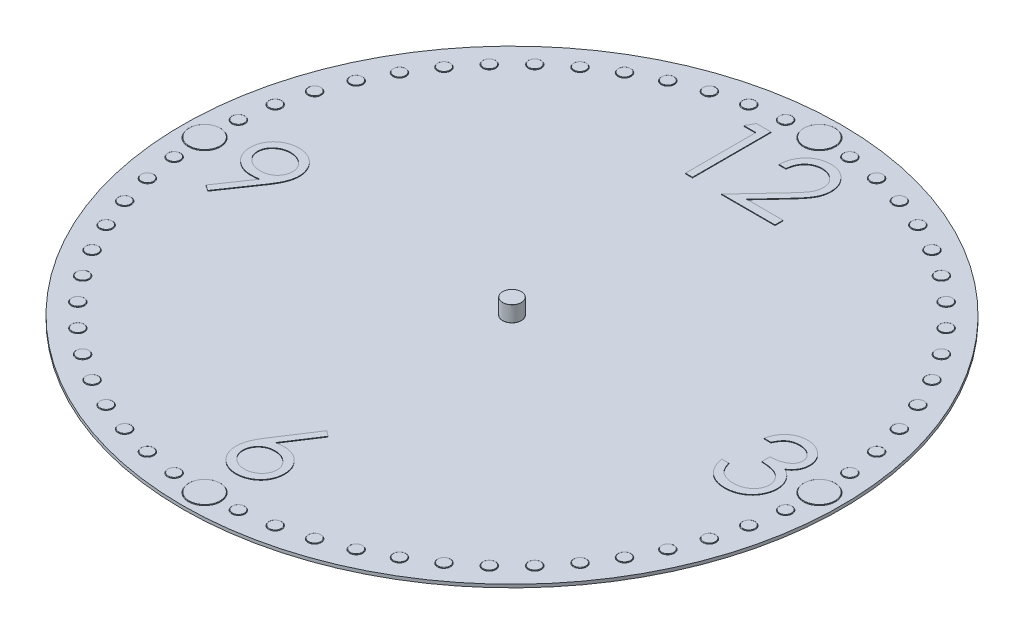
SolidWorks part; units mm, degrees
ref_plane "Front Plane" through (0, 0, 0) normal (0, 0, 1) x (1, 0, 0)
ref_plane "Top Plane" through (0, 0, 0) normal (0, 1, 0) x (1, 0, 0)
ref_plane "Right Plane" through (0, 0, 0) normal (1, 0, 0) x (0, 0, -1)
sketch "Sketch1" plane through (0, 0, 0) normal (0, 1, 0) x (1, 0, 0)
  circle A0 centre (0, 0) radius 13.335
  dimension "D1" = 26.67
extrude "Extrude1" add sketch "Sketch1" along normal blind 0.127
sketch "Sketch2" plane through (0, 0.127, 0) normal (0, 1, 0) x (-1, 0, 0)
  circle A0 centre (0, -12.4392) radius 0.635
  dimension "D1" = 1.27
extrude "Extrude2" add sketch "Sketch2" along normal blind 0.0254
fillet "Fillet1" radius 0.0127 2 edges at (0, 0.127, -11.8042) (0, 0.1524, -11.8042)
sketch "Sketch4" plane through (0, 0, 0) normal (0, 0, 1) x (1, 0, 0)
  line L0 (0, 0) -> (0, 0.4205) construction
pattern_circular "CirPattern1" count 4 over 360 about axis through (0, 0, 0) along (0, 1, 0) of "Extrude2", "Fillet1"
sketch "Sketch5" plane through (0, 0.127, 0) normal (0, 1, 0) x (-1, 0, 0)
  line L0 (0, -12.4392) -> (0, 0) construction
  line L1 (0, 0) -> (-1.9264, -18.3289) construction
  circle A0 centre (0, 0) radius 12.4392 construction
  circle A1 centre (-1.3003, -12.3711) radius 0.254
  dimension "D2" = 0.508
  dimension "D1" = 6
extrude "Extrude3" add sketch "Sketch5" along normal blind 0.0254
fillet "Fillet2" radius 0.0127 2 edges at (1.3003, 0.1524, -12.1171) (1.3003, 0.127, -12.1171)
pattern_circular "CirPattern2" count 60 over 360 about axis through (0, 0, 0) along (0, 1, 0) skipping 1, 16, 31, 46 of "Extrude3", "Fillet2"
sketch "Sketch6" plane through (0, 0.127, 0) normal (0, 1, 0) x (-1, 0, 0)
  circle A0 centre (0, 0) radius 0.381
  dimension "D1" = 0.762
sketch "Sketch9" plane through (0, 0, 0) normal (0, 1, 0) x (1, 0, 0)
  text T1 "12"
extrude "Extrude13" add sketch "Sketch6" along normal blind 0.635
wrap "Wrap2" sketch "Sketch9" wrap type scribe source sketch "Sketch9" face at (1.3003, 0.127, -12.1044)
sketch "Sketch16" plane through (0, 0, 0) normal (0, 1, 0) x (1, 0, 0)
  text T0 "9\r\n"
wrap "Wrap3" sketch "Sketch16" wrap type scribe source sketch "Sketch16" face at (-1.4785, 0.127, -10.4688)
sketch "Sketch25" plane through (0, 0, 0) normal (0, 1, 0) x (1, 0, 0)
  text T0 "6\r\n"
wrap "Wrap4" sketch "Sketch25" wrap type scribe source sketch "Sketch25" face at (1.2082, 0.127, -9.9933)
sketch "Sketch29" plane through (0, 0, 0) normal (0, 1, 0) x (1, 0, 0)
  text T0 "3\r\n"
wrap "Wrap5" sketch "Sketch29" wrap type scribe source sketch "Sketch29"
sketch "Sketch27" plane through (0, 0.127, 0) normal (0, 1, 0) x (1, 0, 0)
  line L3 (0.3261, -7.8196) -> (-0.6216, -9.2685)
  line L4 (0.5455, -7.992) -> (0.3261, -7.8196)
  line L5 (-0.2934, -9.2748) -> (0.5455, -7.992)
  line L6 (0.3261, -7.8196) -> (-0.6216, -9.2685)
  line L7 (0.5455, -7.992) -> (0.3261, -7.8196)
  line L8 (-0.2934, -9.2748) -> (0.5455, -7.992)
  spline S4 degree 3 poles (169.9791, -3005.9549) (-7.8632, 10.3363) (-3.2139, -11.2264) (0.1384, -10.8215) (0.2038, -10.8069) (0.2664, -10.7862) (0.3268, -10.761) (0.384, -10.729) (0.4385, -10.691) (0.49, -10.6482) (0.5377, -10.6016) (0.5788, -10.5515) (0.6139, -10.4992) (0.6424, -10.4446) (0.6651, -10.3873) (0.6807, -10.3277) (1.1283, -7.5783) (-22.7687, -2.839) (2990.9953, -249.0063) knots -9.527484 -9.527484 -9.527484 -9.527484 0.067962 0.133283 0.197835 0.260892 0.323377 0.38635 0.449638 0.514795 0.57924 0.641814 0.701359 0.760727 0.819222 0.878716 0.938147 8.835 8.835 8.835 8.835 only from (0.0005, -10.8318) to (0.6924, -10.2022)
  spline S5 degree 3 poles (-2499.3081, 1650.7062) (17.4996, -4.4596) (3.0537, -3.4263) (-0.7133, -9.4118) (-0.7535, -9.4805) (-0.7905, -9.546) (-0.8226, -9.6094) (-0.8526, -9.669) (-0.8768, -9.727) (-0.9059, -9.7989) (-0.9334, -9.8867) (-0.9579, -9.9901) (-1.5455, -13.8784) (24.3647, -19.7976) (-2992.663, 211.5949) knots -20.907275 -20.907275 -20.907275 -20.907275 0.087622 0.171402 0.250166 0.325701 0.396343 0.462726 0.525528 0.584189 0.694724 0.800274 0.902182 12.434052 12.434052 12.434052 12.434052 only from (-0.6216, -9.2685) to (-0.9765, -10.1907)
  spline S6 degree 3 poles (-258.6624, 2979.4182) (13.1071, -40.3097) (-3.2002, 23.2871) (-7.566, -43.3144) (-289.8247, 2976.5743) knots -46.482215 -46.482215 -46.482215 -46.482215 0.487341 48.273881 48.273881 48.273881 48.273881 only from (0.0354, -9.2443) to (-0.2934, -9.2748)
  spline S7 degree 3 poles (2995.0429, 176.393) (-24.0353, -19.5314) (1.4984, -13.9156) (0.9619, -9.9946) (0.9401, -9.9045) (0.9103, -9.8184) (0.8718, -9.7362) (0.8245, -9.6582) (0.7681, -9.5843) (0.7044, -9.5148) (0.6342, -9.4519) (0.5602, -9.3957) (0.4816, -9.3495) (0.3997, -9.3109) (0.3141, -9.2807) (0.2245, -9.26) (-3.6259, -8.7176) (-9.3454, -34.5352) (204.3295, 2983.6417) knots -7.793325 -7.793325 -7.793325 -7.793325 0.065659 0.129258 0.191437 0.252717 0.31332 0.37449 0.436909 0.500928 0.564976 0.627137 0.688454 0.749057 0.809933 0.871595 0.934769 8.657147 8.657147 8.657147 8.657147 only from (0.9774, -10.185) to (0.0354, -9.2443)
  spline S8 degree 3 poles (275.617, -2998.3814) (-11.4415, 20.002) (-4.0366, -11.959) (0.2468, -11.1276) (0.3714, -11.0868) (0.49, -11.03) (0.6002, -10.9605) (0.6977, -10.8773) (0.7828, -10.7841) (0.8527, -10.6788) (0.9089, -10.5655) (0.9482, -10.4442) (1.7782, -6.2687) (-31.0303, 1.1492) (2987.7444, -289.4489) knots -8.162033 -8.162033 -8.162033 -8.162033 0.085972 0.169956 0.254217 0.339243 0.423978 0.505828 0.586636 0.66771 0.749601 0.830875 0.914052 8.960034 8.960034 8.960034 8.960034 only from (-0.0148, -11.1574) to (0.9774, -10.185)
  spline S9 degree 3 poles (-2989.2364, -273.907) (29.3041, 0.935) (-1.7585, -6.2065) (-0.9475, -10.4433) (-0.9065, -10.5639) (-0.8518, -10.6796) (-0.7829, -10.7872) (-0.7001, -10.8825) (-0.6057, -10.9656) (-0.5002, -11.0346) (-0.3863, -11.0892) (-0.2666, -11.1289) (3.8585, -11.9394) (11.0596, 19.9916) (-272.2933, -2998.7105) knots -8.234795 -8.234795 -8.234795 -8.234795 0.084361 0.16749 0.250533 0.3354 0.419627 0.502172 0.584085 0.66726 0.750434 0.832948 0.915665 9.020067 9.020067 9.020067 9.020067 only from (-0.9765, -10.1907) to (-0.0148, -11.1574)
  spline S10 degree 3 poles (-0.6216, -9.2685) (-0.6375, -9.293) (-0.6688, -9.3411) (-0.7133, -9.4118) (-0.7535, -9.4805) (-0.7905, -9.546) (-0.8226, -9.6094) (-0.8526, -9.669) (-0.8768, -9.727) (-0.9059, -9.7989) (-0.9334, -9.8867) (-0.9579, -9.9901) (-0.9732, -10.0912) (-0.9754, -10.158) (-0.9765, -10.1907) knots 0 0 0 0 0.087622 0.171402 0.250166 0.325701 0.396343 0.462726 0.525528 0.584189 0.694724 0.800274 0.902182 1 1 1 1
  spline S11 degree 3 poles (0.0354, -9.2443) (-0.0183, -9.2457) (-0.1286, -9.2486) (-0.2375, -9.2659) (-0.2934, -9.2748) knots 0 0 0 0 0.487341 1 1 1 1
  spline S12 degree 3 poles (0.9774, -10.185) (0.9765, -10.1525) (0.9747, -10.0886) (0.9619, -9.9946) (0.9401, -9.9045) (0.9103, -9.8184) (0.8718, -9.7362) (0.8245, -9.6582) (0.7681, -9.5843) (0.7044, -9.5148) (0.6342, -9.4519) (0.5602, -9.3957) (0.4816, -9.3495) (0.3997, -9.3109) (0.3141, -9.2807) (0.2245, -9.26) (0.1312, -9.2469) (0.0677, -9.2452) (0.0354, -9.2443) knots 0 0 0 0 0.065659 0.129258 0.191437 0.252717 0.31332 0.37449 0.436909 0.500928 0.564976 0.627137 0.688454 0.749057 0.809933 0.871595 0.934769 1 1 1 1
  spline S13 degree 3 poles (-0.0148, -11.1574) (0.0296, -11.1559) (0.1174, -11.1527) (0.2468, -11.1276) (0.3714, -11.0868) (0.49, -11.03) (0.6002, -10.9605) (0.6977, -10.8773) (0.7828, -10.7841) (0.8527, -10.6788) (0.9089, -10.5655) (0.9482, -10.4442) (0.9736, -10.3168) (0.9761, -10.2294) (0.9774, -10.185) knots 0 0 0 0 0.085972 0.169956 0.254217 0.339243 0.423978 0.505828 0.586636 0.66771 0.749601 0.830875 0.914052 1 1 1 1
  spline S14 degree 3 poles (-0.9765, -10.1907) (-0.9748, -10.2334) (-0.9714, -10.3182) (-0.9475, -10.4433) (-0.9065, -10.5639) (-0.8518, -10.6796) (-0.7829, -10.7872) (-0.7001, -10.8825) (-0.6057, -10.9656) (-0.5002, -11.0346) (-0.3863, -11.0892) (-0.2666, -11.1289) (-0.1422, -11.1533) (-0.0575, -11.1561) (-0.0148, -11.1574) knots 0 0 0 0 0.084361 0.16749 0.250533 0.3354 0.419627 0.502172 0.584085 0.66726 0.750434 0.832948 0.915665 1 1 1 1
  spline S15 degree 3 poles (2988.8667, 254.5542) (-23.8611, -17.6816) (1.1513, -12.7264) (0.6799, -10.0756) (0.6645, -10.0155) (0.6413, -9.9578) (0.6112, -9.9029) (0.5744, -9.8505) (0.532, -9.8001) (0.4829, -9.7534) (0.4295, -9.7106) (0.3727, -9.6728) (0.3132, -9.641) (0.2512, -9.6144) (0.186, -9.5952) (0.1185, -9.5801) (-3.3998, -9.1793) (-7.9862, -30.4824) (140.2087, 2986.9965) knots -7.403749 -7.403749 -7.403749 -7.403749 0.061138 0.119994 0.178225 0.236256 0.294929 0.354716 0.41673 0.480664 0.545832 0.609758 0.672971 0.736017 0.799839 0.864775 0.931088 10.779567 10.779567 10.779567 10.779567 only from (0.6924, -10.2022) to (-0.0243, -9.5699)
  spline S16 degree 3 poles (-140.2945, 2987.0276) (7.8507, -30.5806) (3.3064, -9.1791) (-0.1651, -9.58) (-0.2307, -9.5951) (-0.2934, -9.6143) (-0.3522, -9.6407) (-0.4073, -9.6728) (-0.4591, -9.7105) (-0.5069, -9.7535) (-0.5503, -9.8004) (-0.5877, -9.8507) (-0.6199, -9.9032) (-0.6461, -9.9582) (-0.6665, -10.0158) (-0.6813, -10.0756) (-1.0857, -13.1538) (20.4729, -17.6016) (-2995.1872, 170.2015) knots -9.973756 -9.973756 -9.973756 -9.973756 0.070599 0.137901 0.203196 0.26679 0.329106 0.390654 0.452653 0.515748 0.577926 0.63893 0.698351 0.757296 0.816394 0.876267 0.936817 9.857126 9.857126 9.857126 9.857126 only from (-0.0243, -9.5699) to (-0.6915, -10.2022)
  spline S17 degree 3 poles (-2990.7427, -253.2228) (22.7923, -2.8091) (-1.1279, -7.5816) (-0.6797, -10.3277) (-0.6643, -10.3873) (-0.6413, -10.4443) (-0.6139, -10.4996) (-0.5777, -10.551) (-0.5376, -10.6019) (-0.4896, -10.6481) (-0.4382, -10.6912) (-0.3832, -10.7288) (-0.3259, -10.761) (-0.2655, -10.7862) (-0.2029, -10.8069) (-0.1375, -10.8215) (3.2146, -11.2264) (7.8659, 10.3372) (-170.2687, -3005.9248) knots -7.825614 -7.825614 -7.825614 -7.825614 0.061842 0.121262 0.180746 0.239231 0.298308 0.358183 0.420359 0.484792 0.549938 0.613718 0.676681 0.739154 0.8022 0.86674 0.93205 10.525288 10.525288 10.525288 10.525288 only from (-0.6915, -10.2022) to (0.0005, -10.8318)
  spline S18 degree 3 poles (0.0005, -10.8318) (0.024, -10.8311) (0.0702, -10.8297) (0.1384, -10.8215) (0.2038, -10.8069) (0.2664, -10.7862) (0.3268, -10.761) (0.384, -10.729) (0.4385, -10.691) (0.49, -10.6482) (0.5377, -10.6016) (0.5788, -10.5515) (0.6139, -10.4992) (0.6424, -10.4446) (0.6651, -10.3873) (0.6807, -10.3277) (0.6908, -10.2657) (0.6919, -10.2236) (0.6924, -10.2022) knots 0 0 0 0 0.067962 0.133283 0.197835 0.260892 0.323377 0.38635 0.449638 0.514795 0.57924 0.641814 0.701359 0.760727 0.819222 0.878716 0.938147 1 1 1 1
  spline S19 degree 3 poles (0.6924, -10.2022) (0.6919, -10.1805) (0.691, -10.1379) (0.6799, -10.0756) (0.6645, -10.0155) (0.6413, -9.9578) (0.6112, -9.9029) (0.5744, -9.8505) (0.532, -9.8001) (0.4829, -9.7534) (0.4295, -9.7106) (0.3727, -9.6728) (0.3132, -9.641) (0.2512, -9.6144) (0.186, -9.5952) (0.1185, -9.5801) (0.0479, -9.5721) (0.0001, -9.5707) (-0.0243, -9.5699) knots 0 0 0 0 0.061138 0.119994 0.178225 0.236256 0.294929 0.354716 0.41673 0.480664 0.545832 0.609758 0.672971 0.736017 0.799839 0.864775 0.931088 1 1 1 1
  spline S20 degree 3 poles (-0.0243, -9.5699) (-0.0485, -9.5707) (-0.0958, -9.572) (-0.1651, -9.58) (-0.2307, -9.5951) (-0.2934, -9.6143) (-0.3522, -9.6407) (-0.4073, -9.6728) (-0.4591, -9.7105) (-0.5069, -9.7535) (-0.5503, -9.8004) (-0.5877, -9.8507) (-0.6199, -9.9032) (-0.6461, -9.9582) (-0.6665, -10.0158) (-0.6813, -10.0756) (-0.6895, -10.1381) (-0.6908, -10.1805) (-0.6915, -10.2022) knots 0 0 0 0 0.070599 0.137901 0.203196 0.26679 0.329106 0.390654 0.452653 0.515748 0.577926 0.63893 0.698351 0.757296 0.816394 0.876267 0.936817 1 1 1 1
  spline S21 degree 3 poles (-0.6915, -10.2022) (-0.691, -10.2236) (-0.6898, -10.2657) (-0.6797, -10.3277) (-0.6643, -10.3873) (-0.6413, -10.4443) (-0.6139, -10.4996) (-0.5777, -10.551) (-0.5376, -10.6019) (-0.4896, -10.6481) (-0.4382, -10.6912) (-0.3832, -10.7288) (-0.3259, -10.761) (-0.2655, -10.7862) (-0.2029, -10.8069) (-0.1375, -10.8215) (-0.0693, -10.8297) (-0.0231, -10.8311) (0.0005, -10.8318) knots 0 0 0 0 0.061842 0.121262 0.180746 0.239231 0.298308 0.358183 0.420359 0.484792 0.549938 0.613718 0.676681 0.739154 0.8022 0.86674 0.93205 1 1 1 1
  dimension "D1" = 0
  dimension "D2" = 0
extrude "Extrude18" add sketch "Sketch27" along normal blind 0.0254
sketch "Sketch20" plane through (0, 0.127, 0) normal (0, 1, 0) x (1, 0, 0)
  line L3 (-10.5003, -1.8117) -> (-9.5227, -0.3819)
  line L4 (-10.728, -1.6533) -> (-10.5003, -1.8117)
  line L5 (-9.8452, -0.3628) -> (-10.728, -1.6533)
  line L6 (-10.5003, -1.8117) -> (-9.5227, -0.3819)
  line L7 (-10.728, -1.6533) -> (-10.5003, -1.8117)
  line L8 (-9.8452, -0.3628) -> (-10.728, -1.6533)
  spline S4 degree 3 poles (-164.5335, 2997.1407) (-2.1865, -19.8295) (-6.8301, 1.593) (-10.2971, 1.1903) (-10.3641, 1.1754) (-10.4286, 1.1551) (-10.4906, 1.1289) (-10.5499, 1.0971) (-10.6062, 1.0592) (-10.659, 1.0162) (-10.708, 0.9699) (-10.7499, 0.9193) (-10.7858, 0.867) (-10.8156, 0.8124) (-10.8383, 0.755) (-10.8552, 0.6954) (-11.2921, -2.1329) (11.9721, -6.6168) (-3003.8264, 203.8311) knots -9.696381 -9.696381 -9.696381 -9.696381 0.068712 0.134812 0.199538 0.263335 0.326747 0.390328 0.454126 0.519203 0.58351 0.645497 0.70529 0.763488 0.821856 0.880004 0.939108 8.924521 8.924521 8.924521 8.924521 only from (-10.1555, 1.2005) to (-10.8666, 0.5696)
  spline S5 degree 3 poles (2487.2579, -1663.317) (-28.7469, -1.8575) (-12.65, -5.2962) (-9.4279, -0.2372) (-9.3861, -0.1682) (-9.3492, -0.1017) (-9.3148, -0.0385) (-9.2853, 0.0224) (-9.2587, 0.0802) (-9.2305, 0.1534) (-9.2012, 0.2421) (-9.1754, 0.3468) (-8.5901, 4.307) (-34.5404, 10.2167) (2983.1763, -211.6672) knots -17.442044 -17.442044 -17.442044 -17.442044 0.087946 0.171747 0.250583 0.32591 0.396143 0.462994 0.525418 0.583838 0.694397 0.800583 0.90168 12.476684 12.476684 12.476684 12.476684 only from (-9.5227, -0.3819) to (-9.157, 0.5505)
  spline S6 degree 3 poles (187.7732, -2993.6429) (-23.6022, 28.2124) (-7.8166, -30.1038) (-0.5757, 30.4935) (222.3825, -2991.1898) knots -51.049841 -51.049841 -51.049841 -51.049841 0.492142 52.587835 52.587835 52.587835 52.587835 only from (-10.1791, -0.387) to (-9.8452, -0.3628)
  spline S7 degree 3 poles (-3004.3671, -199.4635) (14.6766, 9.8307) (-11.6899, 4.1624) (-11.1354, 0.3632) (-11.1131, 0.2734) (-11.0825, 0.187) (-11.0421, 0.1052) (-10.9936, 0.0266) (-10.9351, -0.047) (-10.8695, -0.1166) (-10.7974, -0.1799) (-10.7205, -0.2352) (-10.6396, -0.2823) (-10.5549, -0.3202) (-10.4664, -0.3507) (-10.374, -0.3712) (-6.4249, -0.9165) (-0.5961, 25.0954) (-213.894, -2993.3167) knots -7.432221 -7.432221 -7.432221 -7.432221 0.064609 0.12725 0.188534 0.248578 0.309139 0.369772 0.431966 0.495825 0.559795 0.622662 0.68409 0.74564 0.807138 0.869869 0.933705 8.725564 8.725564 8.725564 8.725564 only from (-11.1515, 0.5537) to (-10.1791, -0.387)
  spline S8 degree 3 poles (-267.5318, 2990.4136) (1.2514, -29.22) (-6.019, 2.32) (-10.4063, 1.4966) (-10.533, 1.4546) (-10.6539, 1.3977) (-10.7659, 1.3269) (-10.8661, 1.2446) (-10.9524, 1.1506) (-11.0242, 1.0463) (-11.0812, 0.9331) (-11.122, 0.8127) (-11.9531, -3.4468) (20.1884, -10.7958) (-2998.7985, 271.7019) knots -8.280467 -8.280467 -8.280467 -8.280467 0.086062 0.17094 0.255778 0.341735 0.427007 0.509416 0.590092 0.671171 0.751825 0.832673 0.914751 9.049697 9.049697 9.049697 9.049697 only from (-10.1409, 1.5261) to (-11.1515, 0.5537)
  spline S9 degree 3 poles (2977.135, 285.5898) (-40.2348, -10.7025) (-8.356, -3.3421) (-9.1869, 0.8041) (-9.2278, 0.9254) (-9.2845, 1.0417) (-9.3551, 1.1499) (-9.4389, 1.247) (-9.5358, 1.3306) (-9.6435, 1.4007) (-9.7598, 1.4567) (-9.8822, 1.4972) (-14.2129, 2.3112) (-21.453, -29.0003) (251.6617, 2989.9347) knots -7.942459 -7.942459 -7.942459 -7.942459 0.083474 0.165402 0.248081 0.332 0.416297 0.498735 0.580591 0.664318 0.748057 0.830997 0.914468 9.28503 9.28503 9.28503 9.28503 only from (-9.157, 0.5505) to (-10.1409, 1.5261)
  spline S10 degree 3 poles (-9.5227, -0.3819) (-9.5061, -0.3572) (-9.4736, -0.3089) (-9.4279, -0.2372) (-9.3861, -0.1682) (-9.3492, -0.1017) (-9.3148, -0.0385) (-9.2853, 0.0224) (-9.2587, 0.0802) (-9.2305, 0.1534) (-9.2012, 0.2421) (-9.1754, 0.3468) (-9.1602, 0.4495) (-9.1581, 0.5171) (-9.157, 0.5505) knots 0 0 0 0 0.087946 0.171747 0.250583 0.32591 0.396143 0.462994 0.525418 0.583838 0.694397 0.800583 0.90168 1 1 1 1
  spline S11 degree 3 poles (-10.1791, -0.387) (-10.1241, -0.3858) (-10.0124, -0.3833) (-9.9015, -0.3697) (-9.8452, -0.3628) knots 0 0 0 0 0.492142 1 1 1 1
  spline S12 degree 3 poles (-11.1515, 0.5537) (-11.1507, 0.5212) (-11.1491, 0.4572) (-11.1354, 0.3632) (-11.1131, 0.2734) (-11.0825, 0.187) (-11.0421, 0.1052) (-10.9936, 0.0266) (-10.9351, -0.047) (-10.8695, -0.1166) (-10.7974, -0.1799) (-10.7205, -0.2352) (-10.6396, -0.2823) (-10.5549, -0.3202) (-10.4664, -0.3507) (-10.374, -0.3712) (-10.2778, -0.3845) (-10.2124, -0.3862) (-10.1791, -0.387) knots 0 0 0 0 0.064609 0.12725 0.188534 0.248578 0.309139 0.369772 0.431966 0.495825 0.559795 0.622662 0.68409 0.74564 0.807138 0.869869 0.933705 1 1 1 1
  spline S13 degree 3 poles (-10.1409, 1.5261) (-10.1858, 1.5245) (-10.2748, 1.5212) (-10.4063, 1.4966) (-10.533, 1.4546) (-10.6539, 1.3977) (-10.7659, 1.3269) (-10.8661, 1.2446) (-10.9524, 1.1506) (-11.0242, 1.0463) (-11.0812, 0.9331) (-11.122, 0.8127) (-11.1469, 0.6853) (-11.15, 0.5981) (-11.1515, 0.5537) knots 0 0 0 0 0.086062 0.17094 0.255778 0.341735 0.427007 0.509416 0.590092 0.671171 0.751825 0.832673 0.914751 1 1 1 1
  spline S14 degree 3 poles (-9.157, 0.5505) (-9.1586, 0.5934) (-9.1618, 0.6785) (-9.1869, 0.8041) (-9.2278, 0.9254) (-9.2845, 1.0417) (-9.3551, 1.1499) (-9.4389, 1.247) (-9.5358, 1.3306) (-9.6435, 1.4007) (-9.7598, 1.4567) (-9.8822, 1.4972) (-10.01, 1.5212) (-10.0969, 1.5245) (-10.1409, 1.5261) knots 0 0 0 0 0.083474 0.165402 0.248081 0.332 0.416297 0.498735 0.580591 0.664318 0.748057 0.830997 0.914468 1 1 1 1
  spline S15 degree 3 poles (-3002.3399, -224.0732) (12.9244, 7.773) (-11.3112, 3.1582) (-10.8545, 0.4436) (-10.837, 0.384) (-10.8136, 0.3264) (-10.7828, 0.2714) (-10.7449, 0.2192) (-10.7006, 0.1692) (-10.6503, 0.1222) (-10.5952, 0.0791) (-10.5365, 0.0414) (-10.4749, 0.0096) (-10.4105, -0.016) (-10.3435, -0.0365) (-10.2735, -0.0511) (-6.6646, -0.4535) (-1.9005, 20.8521) (-162.1587, -2996.0663) knots -7.443137 -7.443137 -7.443137 -7.443137 0.05954 0.117423 0.17444 0.231734 0.289722 0.3492 0.410516 0.47508 0.540094 0.604444 0.668697 0.73211 0.796739 0.862906 0.930462 10.866089 10.866089 10.866089 10.866089 only from (-10.8666, 0.5696) to (-10.1263, -0.0614)
  spline S16 degree 3 poles (147.0279, -2995.8644) (-18.3349, 21.2679) (-13.5496, -0.4563) (-9.9799, -0.0512) (-9.9119, -0.0367) (-9.8478, -0.0159) (-9.7869, 0.0092) (-9.7302, 0.0411) (-9.6776, 0.0793) (-9.6288, 0.1221) (-9.5855, 0.1697) (-9.5469, 0.2195) (-9.5141, 0.2717) (-9.4882, 0.327) (-9.4669, 0.3841) (-9.4522, 0.4438) (-9.0491, 3.5149) (-30.4358, 7.9819) (2984.6742, -184.942) knots -10.121139 -10.121139 -10.121139 -10.121139 0.072713 0.141547 0.208363 0.272462 0.33539 0.397711 0.459383 0.522098 0.584315 0.644392 0.703345 0.761509 0.82003 0.878517 0.938265 9.721188 9.721188 9.721188 9.721188 only from (-10.1263, -0.0614) to (-9.4419, 0.5696)
  spline S17 degree 3 poles (2983.532, 203.5527) (-32.2797, -6.6148) (-9.0165, -2.1331) (-9.4533, 0.6954) (-9.4702, 0.755) (-9.4929, 0.8124) (-9.5228, 0.867) (-9.5586, 0.9195) (-9.6012, 0.9697) (-9.6502, 1.0162) (-9.703, 1.0592) (-9.7593, 1.0971) (-9.8186, 1.1289) (-9.8805, 1.1551) (-9.9453, 1.1755) (-10.0127, 1.1903) (-13.5065, 1.5934) (-18.1865, -19.8522) (145.3202, 2997.0521) knots -7.907648 -7.907648 -7.907648 -7.907648 0.06076 0.119735 0.177757 0.235999 0.29407 0.353733 0.415973 0.48014 0.545076 0.608735 0.672178 0.735453 0.799112 0.864284 0.930837 10.749561 10.749561 10.749561 10.749561 only from (-9.4419, 0.5696) to (-10.1555, 1.2005)
  spline S18 degree 3 poles (-10.1555, 1.2005) (-10.1797, 1.1998) (-10.2272, 1.1984) (-10.2971, 1.1903) (-10.3641, 1.1754) (-10.4286, 1.1551) (-10.4906, 1.1289) (-10.5499, 1.0971) (-10.6062, 1.0592) (-10.659, 1.0162) (-10.708, 0.9699) (-10.7499, 0.9193) (-10.7858, 0.867) (-10.8156, 0.8124) (-10.8383, 0.755) (-10.8552, 0.6954) (-10.8648, 0.6333) (-10.866, 0.591) (-10.8666, 0.5696) knots 0 0 0 0 0.068712 0.134812 0.199538 0.263335 0.326747 0.390328 0.454126 0.519203 0.58351 0.645497 0.70529 0.763488 0.821856 0.880004 0.939108 1 1 1 1
  spline S19 degree 3 poles (-10.8666, 0.5696) (-10.8661, 0.5481) (-10.865, 0.5058) (-10.8545, 0.4436) (-10.837, 0.384) (-10.8136, 0.3264) (-10.7828, 0.2714) (-10.7449, 0.2192) (-10.7006, 0.1692) (-10.6503, 0.1222) (-10.5952, 0.0791) (-10.5365, 0.0414) (-10.4749, 0.0096) (-10.4105, -0.016) (-10.3435, -0.0365) (-10.2735, -0.0511) (-10.2007, -0.0593) (-10.1513, -0.0607) (-10.1263, -0.0614) knots 0 0 0 0 0.05954 0.117423 0.17444 0.231734 0.289722 0.3492 0.410516 0.47508 0.540094 0.604444 0.668697 0.73211 0.796739 0.862906 0.930462 1 1 1 1
  spline S20 degree 3 poles (-10.1263, -0.0614) (-10.101, -0.0607) (-10.0519, -0.0593) (-9.9799, -0.0512) (-9.9119, -0.0367) (-9.8478, -0.0159) (-9.7869, 0.0092) (-9.7302, 0.0411) (-9.6776, 0.0793) (-9.6288, 0.1221) (-9.5855, 0.1697) (-9.5469, 0.2195) (-9.5141, 0.2717) (-9.4882, 0.327) (-9.4669, 0.3841) (-9.4522, 0.4438) (-9.444, 0.5059) (-9.4426, 0.5481) (-9.4419, 0.5696) knots 0 0 0 0 0.072713 0.141547 0.208363 0.272462 0.33539 0.397711 0.459383 0.522098 0.584315 0.644392 0.703345 0.761509 0.82003 0.878517 0.938265 1 1 1 1
  spline S21 degree 3 poles (-9.4419, 0.5696) (-9.4425, 0.591) (-9.4437, 0.6333) (-9.4533, 0.6954) (-9.4702, 0.755) (-9.4929, 0.8124) (-9.5228, 0.867) (-9.5586, 0.9195) (-9.6012, 0.9697) (-9.6502, 1.0162) (-9.703, 1.0592) (-9.7593, 1.0971) (-9.8186, 1.1289) (-9.8805, 1.1551) (-9.9453, 1.1755) (-10.0127, 1.1903) (-10.0833, 1.1984) (-10.1311, 1.1998) (-10.1555, 1.2005) knots 0 0 0 0 0.06076 0.119735 0.177757 0.235999 0.29407 0.353733 0.415973 0.48014 0.545076 0.608735 0.672178 0.735453 0.799112 0.864284 0.930837 1 1 1 1
  dimension "D1" = 0
  dimension "D2" = 0
extrude "Extrude16" add sketch "Sketch20" along normal blind 0.0254
sketch "Sketch24" plane through (0, 0.127, 0) normal (0, 1, 0) x (1, 0, 0)
  line L0 (-1.1568, 11.6356) -> (-1.1568, 8.4606) construction
  line L1 (-1.1568, 8.4606) -> (-1.4417, 8.4606) construction
  line L2 (-1.1568, 11.6356) -> (-1.1568, 8.4606)
  line L3 (-1.1568, 8.4606) -> (-1.4417, 8.4606)
  line L4 (-1.4417, 8.4606) -> (-1.4417, 11.31) construction
  line L5 (-1.4417, 11.31) -> (-1.9302, 11.31) construction
  line L6 (-1.9302, 11.31) -> (-1.7438, 11.6356) construction
  line L7 (-1.7438, 11.6356) -> (-1.1568, 11.6356) construction
  line L8 (-1.4417, 8.4606) -> (-1.4417, 11.31)
  line L9 (-1.4417, 11.31) -> (-1.9302, 11.31)
  line L10 (-1.9302, 11.31) -> (-1.7438, 11.6356)
  line L11 (-1.7438, 11.6356) -> (-1.1568, 11.6356)
  line L12 (2.1811, 8.4606) -> (0.0237, 8.4606) construction
  line L13 (2.1811, 8.7863) -> (2.1811, 8.4606) construction
  line L14 (0.7036, 8.7863) -> (2.1811, 8.7863) construction
  line L15 (1.498, 9.6341) -> (0.7036, 8.7863) construction
  line L16 (0.4307, 10.6587) -> (0.1458, 10.6587) construction
  line L17 (0.0237, 8.4606) -> (1.255, 9.7747) construction
  line L18 (2.1811, 8.4606) -> (0.0237, 8.4606)
  line L19 (2.1811, 8.7863) -> (2.1811, 8.4606)
  line L20 (0.7036, 8.7863) -> (2.1811, 8.7863)
  line L21 (1.498, 9.6341) -> (0.7036, 8.7863)
  line L22 (0.4307, 10.6587) -> (0.1458, 10.6587)
  line L23 (0.0237, 8.4606) -> (1.255, 9.7747)
  spline S0 degree 3 poles (1992.8888, -180.7363) (-21.9954, 20.4269) (2.8534, 14.1906) (2.1097, 10.5125) (2.069, 10.3877) (2.0201, 10.2872) (1.9706, 10.2063) (1.9261, 10.1396) (1.874, 10.0679) (1.8135, 9.9912) (1.7459, 9.9091) (1.6706, 9.8216) (-3.9681, 3.6108) (-17.6358, 4.9304) (1447.9539, -1371.4309) knots -8.056366 -8.056366 -8.056366 -8.056366 0.098702 0.195672 0.292422 0.391343 0.444462 0.504229 0.570352 0.642546 0.722288 0.807921 0.90047 19.46034 19.46034 19.46034 19.46034 only from (2.1404, 10.7732) to (1.498, 9.6341) construction
  spline S1 degree 3 poles (126.2886, 2007.7465) (-7.0917, -8.1164) (-2.1637, 12.1896) (1.3843, 11.7009) (1.4793, 11.6793) (1.5694, 11.6491) (1.6538, 11.6085) (1.7331, 11.5597) (1.8083, 11.5033) (1.876, 11.4368) (1.9381, 11.3659) (1.9917, 11.2901) (2.0376, 11.2119) (2.0759, 11.1306) (2.1041, 11.0454) (2.1255, 10.9577) (2.5806, 7.5216) (-16.287, 2.9111) (1998.7713, 125.1206) knots -6.934537 -6.934537 -6.934537 -6.934537 0.069475 0.136517 0.200789 0.26383 0.325735 0.387291 0.449509 0.512968 0.576275 0.63758 0.697903 0.757172 0.816599 0.876653 0.93729 7.720344 7.720344 7.720344 7.720344 only from (1.1812, 11.7171) to (2.1404, 10.7732) construction
  spline S2 degree 3 poles (-1992.0742, 186.1515) (19.9257, 1.3335) (-0.4325, 7.071) (0.1684, 10.879) (0.1928, 10.9825) (0.2274, 11.0803) (0.2703, 11.1734) (0.3218, 11.2614) (0.3827, 11.344) (0.4518, 11.4203) (0.5269, 11.4903) (0.6079, 11.5508) (0.6931, 11.6019) (0.7821, 11.6446) (0.8759, 11.6766) (0.9738, 11.7004) (4.5324, 12.1982) (9.4344, -8.4475) (-118.3449, 2008.0165) knots -6.801028 -6.801028 -6.801028 -6.801028 0.068791 0.135103 0.198979 0.261904 0.323495 0.385195 0.446969 0.509765 0.572251 0.633405 0.693251 0.752583 0.812579 0.873275 0.93555 7.331821 7.331821 7.331821 7.331821 only from (0.1458, 10.6587) to (1.1812, 11.7171) construction
  spline S3 degree 3 poles (-109.3262, 2008.2602) (7.987, -5.4652) (3.9908, 11.7502) (1.0214, 11.3806) (0.9531, 11.3652) (0.888, 11.3442) (0.8258, 11.3175) (0.767, 11.2842) (0.7116, 11.2445) (0.6595, 11.1994) (0.6116, 11.1493) (0.5694, 11.0934) (0.5326, 11.0328) (0.5005, 10.9676) (0.4744, 10.8972) (0.4545, 10.822) (-0.174, 7.6401) (17.6391, 1.9366) (-1982.0079, 274.9879) knots -7.564621 -7.564621 -7.564621 -7.564621 0.064439 0.126547 0.186887 0.245878 0.304041 0.362191 0.420976 0.48066 0.5406 0.600689 0.661936 0.724443 0.789038 0.856314 0.926352 9.195555 9.195555 9.195555 9.195555 only from (1.1666, 11.3914) to (0.4307, 10.6587) construction
  spline S4 degree 3 poles (1995.8262, 165.3949) (-15.9465, 4.4957) (2.2356, 8.4289) (1.8437, 10.8747) (1.8285, 10.9351) (1.8068, 10.9935) (1.7781, 11.0492) (1.7432, 11.1024) (1.7029, 11.1538) (1.6564, 11.202) (1.6052, 11.2462) (1.5511, 11.2853) (1.4939, 11.318) (1.4338, 11.3448) (1.371, 11.3658) (1.3054, 11.3804) (-1.4936, 11.7551) (-5.4909, -5.7111) (129.4243, 2007.2166) knots -6.890586 -6.890586 -6.890586 -6.890586 0.061965 0.122122 0.180988 0.239933 0.299906 0.359989 0.421776 0.486576 0.551535 0.615018 0.677259 0.73973 0.80305 0.866495 0.931973 8.870794 8.870794 8.870794 8.870794 only from (1.8554, 10.7478) to (1.1666, 11.3914) construction
  spline S5 degree 3 poles (1435.4585, -1384.0192) (-17.5287, 6.4466) (-3.8927, 4.2249) (1.424, 9.9538) (1.4972, 10.0352) (1.5625, 10.1102) (1.6186, 10.1797) (1.6684, 10.2415) (1.7083, 10.2985) (1.7515, 10.3644) (1.7935, 10.445) (1.8295, 10.5435) (2.4892, 13.5872) (-20.7785, 19.1318) (1991.5943, -191.0898) knots -19.675963 -19.675963 -19.675963 -19.675963 0.110803 0.212829 0.306101 0.390647 0.466924 0.534481 0.593587 0.644557 0.7362 0.825024 0.911986 8.658374 8.658374 8.658374 8.658374 only from (1.255, 9.7747) to (1.8554, 10.7478) construction
  spline S6 degree 3 poles (2.1404, 10.7732) (2.1388, 10.729) (2.1358, 10.6413) (2.1097, 10.5125) (2.069, 10.3877) (2.0201, 10.2872) (1.9706, 10.2063) (1.9261, 10.1396) (1.874, 10.0679) (1.8135, 9.9912) (1.7459, 9.9091) (1.6706, 9.8216) (1.587, 9.7295) (1.5284, 9.6667) (1.498, 9.6341) knots 0 0 0 0 0.098702 0.195672 0.292422 0.391343 0.444462 0.504229 0.570352 0.642546 0.722288 0.807921 0.90047 1 1 1 1
  spline S7 degree 3 poles (1.1812, 11.7171) (1.2161, 11.7162) (1.2845, 11.7146) (1.3843, 11.7009) (1.4793, 11.6793) (1.5694, 11.6491) (1.6538, 11.6085) (1.7331, 11.5597) (1.8083, 11.5033) (1.876, 11.4368) (1.9381, 11.3659) (1.9917, 11.2901) (2.0376, 11.2119) (2.0759, 11.1306) (2.1041, 11.0454) (2.1255, 10.9577) (2.1376, 10.8664) (2.1394, 10.8046) (2.1404, 10.7732) knots 0 0 0 0 0.069475 0.136517 0.200789 0.26383 0.325735 0.387291 0.449509 0.512968 0.576275 0.63758 0.697903 0.757172 0.816599 0.876653 0.93729 1 1 1 1
  spline S8 degree 3 poles (0.1458, 10.6587) (0.1477, 10.6965) (0.1513, 10.7708) (0.1684, 10.879) (0.1928, 10.9825) (0.2274, 11.0803) (0.2703, 11.1734) (0.3218, 11.2614) (0.3827, 11.344) (0.4518, 11.4203) (0.5269, 11.4903) (0.6079, 11.5508) (0.6931, 11.6019) (0.7821, 11.6446) (0.8759, 11.6766) (0.9738, 11.7004) (1.0761, 11.7147) (1.1458, 11.7163) (1.1812, 11.7171) knots 0 0 0 0 0.068791 0.135103 0.198979 0.261904 0.323495 0.385195 0.446969 0.509765 0.572251 0.633405 0.693251 0.752583 0.812579 0.873275 0.93555 1 1 1 1
  spline S9 degree 3 poles (1.1666, 11.3914) (1.1418, 11.3908) (1.093, 11.3895) (1.0214, 11.3806) (0.9531, 11.3652) (0.888, 11.3442) (0.8258, 11.3175) (0.767, 11.2842) (0.7116, 11.2445) (0.6595, 11.1994) (0.6116, 11.1493) (0.5694, 11.0934) (0.5326, 11.0328) (0.5005, 10.9676) (0.4744, 10.8972) (0.4545, 10.822) (0.4387, 10.7421) (0.4334, 10.687) (0.4307, 10.6587) knots 0 0 0 0 0.064439 0.126547 0.186887 0.245878 0.304041 0.362191 0.420976 0.48066 0.5406 0.600689 0.661936 0.724443 0.789038 0.856314 0.926352 1 1 1 1
  spline S10 degree 3 poles (1.8554, 10.7478) (1.8548, 10.7694) (1.8537, 10.8121) (1.8437, 10.8747) (1.8285, 10.9351) (1.8068, 10.9935) (1.7781, 11.0492) (1.7432, 11.1024) (1.7029, 11.1538) (1.6564, 11.202) (1.6052, 11.2462) (1.5511, 11.2853) (1.4939, 11.318) (1.4338, 11.3448) (1.371, 11.3658) (1.3054, 11.3804) (1.237, 11.3895) (1.1904, 11.3908) (1.1666, 11.3914) knots 0 0 0 0 0.061965 0.122122 0.180988 0.239933 0.299906 0.359989 0.421776 0.486576 0.551535 0.615018 0.677259 0.73973 0.80305 0.866495 0.931973 1 1 1 1
  spline S11 degree 3 poles (1.255, 9.7747) (1.285, 9.806) (1.3426, 9.8661) (1.424, 9.9538) (1.4972, 10.0352) (1.5625, 10.1102) (1.6186, 10.1797) (1.6684, 10.2415) (1.7083, 10.2985) (1.7515, 10.3644) (1.7935, 10.445) (1.8295, 10.5435) (1.8515, 10.6448) (1.8541, 10.7133) (1.8554, 10.7478) knots 0 0 0 0 0.110803 0.212829 0.306101 0.390647 0.466924 0.534481 0.593587 0.644557 0.7362 0.825024 0.911986 1 1 1 1
extrude "Extrude17" add sketch "Sketch24" along normal blind 0.0254
sketch "Sketch30" plane through (0, 0.127, 0) normal (0, 1, 0) x (1, 0, 0)
  line L3 (9.4338, 0.7616) -> (9.7187, 0.7616)
  line L4 (9.5966, -0.8259) -> (9.3117, -0.8259)
  line L5 (10.2072, 0.2324) -> (10.2072, -0.0932)
  line L6 (9.4338, 0.7616) -> (9.7187, 0.7616)
  line L7 (9.5966, -0.8259) -> (9.3117, -0.8259)
  line L8 (10.2072, 0.2324) -> (10.2072, -0.0932)
  spline S14 degree 3 poles (166.9343, 2997.0262) (2.7365, -19.2613) (7.2043, 1.6043) (10.5143, 1.2414) (10.5762, 1.23) (10.6353, 1.2142) (10.6912, 1.1932) (10.7442, 1.1676) (10.7943, 1.1378) (10.8401, 1.1026) (10.8826, 1.0657) (10.9198, 1.0261) (10.951, 0.9847) (10.9771, 0.9416) (10.9966, 0.8965) (11.0108, 0.8498) (11.4297, -1.291) (-12.176, -5.6584) (2998.4254, 273.219) knots -10.883923 -10.883923 -10.883923 -10.883923 0.075072 0.147677 0.217498 0.284969 0.351483 0.416689 0.481138 0.545824 0.609005 0.669091 0.726699 0.781924 0.836753 0.890034 0.944725 8.088697 8.088697 8.088697 8.088697 only from (10.3827, 1.2501) to (11.0213, 0.7521)
  spline S15 degree 3 poles (-2701.9816, 1283.9369) (23.794, -14.1997) (8.0279, -2.4851) (9.7775, 0.8841) (9.8091, 0.9389) (9.8438, 0.988) (9.8782, 1.0337) (9.9156, 1.0731) (9.9538, 1.1086) (10.0072, 1.1492) (10.0796, 1.1903) (10.1742, 1.2248) (13.7416, 1.9815) (20.5523, -29.0843) (-286.345, 2986.4041) knots -12.66767 -12.66767 -12.66767 -12.66767 0.079943 0.155331 0.226366 0.294702 0.359396 0.420552 0.479182 0.536234 0.648184 0.760315 0.877288 12.977594 12.977594 12.977594 12.977594 only from (9.7187, 0.7616) to (10.3827, 1.2501)
  spline S16 degree 3 poles (-168.2797, 2996.135) (18.9074, -22.5409) (13.7825, 2.0263) (10.212, 1.5634) (10.1322, 1.547) (10.055, 1.5243) (9.981, 1.4941) (9.91, 1.4576) (9.8416, 1.415) (9.7771, 1.3652) (9.7156, 1.3101) (9.6599, 1.248) (9.6085, 1.1812) (9.5636, 1.1079) (9.5224, 1.0298) (9.4881, 0.9453) (8.1386, -2.882) (31.4871, -13.8782) (-2873.8497, 829.0017) knots -7.759709 -7.759709 -7.759709 -7.759709 0.062835 0.123746 0.183573 0.242729 0.301378 0.359848 0.419006 0.479175 0.539884 0.601255 0.663111 0.726043 0.791015 0.858023 0.927375 9.750884 9.750884 9.750884 9.750884 only from (10.3789, 1.5757) to (9.4338, 0.7616)
  spline S17 degree 3 poles (2993.8996, 323.0183) (-18.6225, -9.469) (12.0621, -2.5184) (11.2785, 0.9584) (11.2403, 1.0589) (11.1885, 1.1566) (11.1224, 1.248) (11.0436, 1.3307) (10.9522, 1.4033) (10.8495, 1.4642) (10.7389, 1.5136) (10.6228, 1.5494) (6.5273, 2.3179) (-0.4749, -28.8877) (273.6807, 2989.8854) knots -7.497364 -7.497364 -7.497364 -7.497364 0.075988 0.151674 0.229179 0.309803 0.391886 0.474253 0.558114 0.645369 0.733907 0.82146 0.909746 9.78258 9.78258 9.78258 9.78258 only from (11.3062, 0.7508) to (10.3789, 1.5757)
  spline S18 degree 3 poles (1824.7342, -2389.3737) (-12.4839, 18.2501) (8.1993, -2.411) (11.0982, 0.2263) (11.1623, 0.3004) (11.2152, 0.38) (11.2561, 0.4652) (11.2856, 0.5556) (11.9415, 4.1423) (-16.8506, 10.237) (3000.9123, -246.4377) knots -14.520808 -14.520808 -14.520808 -14.520808 0.136783 0.265687 0.389625 0.509928 0.62937 0.749392 0.871932 14.490274 14.490274 14.490274 14.490274 only from (10.9354, 0.0976) to (11.3062, 0.7508)
  spline S19 degree 3 poles (2213.9747, 2036.4461) (-6.3429, -26.4902) (13.9523, -2.5106) (11.1274, -0.0144) (7.9421, 2.1985) (-10.5628, -22.688) (1480.463, 2615.3349) knots -24.709045 -24.709045 -24.709045 -24.709045 0.249709 0.496991 0.74612 26.45056 26.45056 26.45056 26.45056 only from (11.2795, -0.1733) to (10.9354, 0.0976)
  spline S20 degree 3 poles (3006.3673, 173.4625) (-10.5322, -9.0135) (11.8822, -4.1079) (11.458, -0.5852) (11.4434, -0.5116) (11.4229, -0.4399) (11.3965, -0.3699) (11.3625, -0.3025) (9.7499, 2.5734) (-12.7507, -8.1483) (2521.7839, 1642.0205) knots -17.165835 -17.165835 -17.165835 -17.165835 0.127125 0.252904 0.376014 0.498288 0.621888 0.745827 0.871864 16.922813 16.922813 16.922813 16.922813 only from (11.4691, -0.7375) to (11.2795, -0.1733)
  spline S21 degree 3 poles (271.6332, -2990.1884) (-1.7948, 30.6685) (5.9818, -2.5941) (10.6646, -1.7312) (10.8021, -1.6903) (10.9306, -1.6314) (11.0493, -1.5577) (11.1557, -1.4696) (11.2483, -1.367) (11.3262, -1.2524) (11.3902, -1.1298) (11.4352, -1.0017) (12.3377, 3.0728) (-21.1831, 10.9443) (2994.1532, -321.5354) knots -8.248381 -8.248381 -8.248381 -8.248381 0.090252 0.177522 0.262564 0.346964 0.430315 0.512398 0.593965 0.677391 0.760381 0.841078 0.920352 8.209858 8.209858 8.209858 8.209858 only from (10.3707, -1.7621) to (11.4691, -0.7375)
  spline S22 degree 3 poles (-2909.4692, -693.5904) (32.303, 13.9561) (8.045, 3.3792) (9.365, -1.0411) (9.4005, -1.1393) (9.4437, -1.2301) (9.4918, -1.3145) (9.5468, -1.3916) (9.6073, -1.4623) (9.6744, -1.5251) (9.7463, -1.5813) (9.8229, -1.6297) (9.9035, -1.6708) (9.9886, -1.7038) (10.078, -1.7298) (10.1717, -1.7492) (14.5725, -2.224) (20.1299, 21.5817) (-123.334, -2998.6341) knots -8.686683 -8.686683 -8.686683 -8.686683 0.073705 0.143654 0.210872 0.275144 0.337494 0.398261 0.457757 0.51683 0.575458 0.633602 0.691452 0.749908 0.809623 0.871037 0.934459 9.34196 9.34196 9.34196 9.34196 only from (9.3117, -0.8259) to (10.3707, -1.7621)
  spline S23 degree 3 poles (-2103.9174, -2129.9904) (29.3197, 11.5492) (11.3515, -3.0435) (9.768, -1.1861) (9.7327, -1.1394) (9.7011, -1.0866) (9.6711, -1.0291) (9.6431, -0.9663) (8.1847, 3.0943) (24.3834, 12.7061) (-2854.8549, -891.9616) knots -13.945895 -13.945895 -13.945895 -13.945895 0.104675 0.213878 0.328473 0.44784 0.574034 0.708684 0.85023 25.848736 25.848736 25.848736 25.848736 only from (9.8453, -1.2647) to (9.5966, -0.8259)
  spline S24 degree 3 poles (-158.1577, -2996.6699) (18.578, 21.4538) (13.7052, -1.8323) (10.2225, -1.4265) (10.1505, -1.4137) (10.0824, -1.3941) (10.0173, -1.371) (9.9564, -1.3407) (7.3413, 0.2382) (18.0527, 20.8725) (-1714.3603, -2456.1501) knots -18.065291 -18.065291 -18.065291 -18.065291 0.138687 0.271392 0.399873 0.524096 0.644337 0.763822 0.881729 16.723289 16.723289 16.723289 16.723289 only from (10.3758, -1.4365) to (9.8453, -1.2647)
  spline S25 degree 3 poles (2999.6548, -262.1117) (-13.6756, 6.7526) (11.654, 1.7765) (11.171, -0.8953) (11.1543, -0.9579) (11.1296, -1.0182) (11.0985, -1.0763) (11.0598, -1.132) (11.0143, -1.1855) (10.9626, -1.2367) (10.9052, -1.2834) (10.8428, -1.3246) (10.7762, -1.3596) (10.7046, -1.3875) (10.629, -1.4101) (10.5483, -1.4248) (6.7487, -1.8751) (1.4442, 22.2265) (186.0294, -2996.1989) knots -6.765396 -6.765396 -6.765396 -6.765396 0.05654 0.112156 0.167356 0.222413 0.278536 0.335925 0.39565 0.458239 0.521931 0.585036 0.649402 0.71424 0.781597 0.851248 0.923928 10.570248 10.570248 10.570248 10.570248 only from (11.1841, -0.7648) to (10.3758, -1.4365)
  spline S26 degree 3 poles (192.8703, 2994.192) (-2.2406, -15.8513) (4.618, 0.3944) (10.3863, -0.1059) (10.4673, -0.1154) (10.542, -0.1267) (10.6103, -0.1401) (10.6727, -0.1544) (10.7284, -0.1714) (10.7935, -0.1968) (10.867, -0.2341) (10.9468, -0.288) (11.0161, -0.3534) (11.0754, -0.4267) (11.1241, -0.5057) (11.1588, -0.5894) (11.8957, -3.6153) (-17.8232, -10.3002) (2990.3021, 351.0066) knots -12.904278 -12.904278 -12.904278 -12.904278 0.070672 0.137142 0.198508 0.255312 0.308108 0.355945 0.400116 0.43977 0.514023 0.586164 0.65712 0.728766 0.798965 0.866515 0.933091 7.804837 7.804837 7.804837 7.804837 only from (10.2072, -0.0932) to (11.1841, -0.7648)
  spline S27 degree 3 poles (2988.6616, -364.2525) (-16.0133, 9.0675) (11.6402, 3.0851) (11.0008, 0.6188) (10.972, 0.5561) (10.9325, 0.496) (10.88, 0.4399) (10.814, 0.3896) (10.7348, 0.3444) (10.6435, 0.3055) (10.5433, 0.2721) (10.4358, 0.2502) (6.163, -0.3501) (-0.1788, 28.0962) (214.5503, -2992.7261) knots -6.907969 -6.907969 -6.907969 -6.907969 0.063304 0.125941 0.189323 0.25633 0.327065 0.403838 0.48835 0.582426 0.681973 0.784213 0.889834 12.772576 12.772576 12.772576 12.772576 only from (11.0213, 0.7521) to (10.2072, 0.2324)
  spline S28 degree 3 poles (10.3827, 1.2501) (10.4052, 1.2496) (10.4495, 1.2485) (10.5143, 1.2414) (10.5762, 1.23) (10.6353, 1.2142) (10.6912, 1.1932) (10.7442, 1.1676) (10.7943, 1.1378) (10.8401, 1.1026) (10.8826, 1.0657) (10.9198, 1.0261) (10.951, 0.9847) (10.9771, 0.9416) (10.9966, 0.8965) (11.0108, 0.8498) (11.0202, 0.8016) (11.0209, 0.7687) (11.0213, 0.7521) knots 0 0 0 0 0.075072 0.147677 0.217498 0.284969 0.351483 0.416689 0.481138 0.545824 0.609005 0.669091 0.726699 0.781924 0.836753 0.890034 0.944725 1 1 1 1
  spline S29 degree 3 poles (9.7187, 0.7616) (9.7283, 0.7831) (9.7468, 0.8249) (9.7775, 0.8841) (9.8091, 0.9389) (9.8438, 0.988) (9.8782, 1.0337) (9.9156, 1.0731) (9.9538, 1.1086) (10.0072, 1.1492) (10.0796, 1.1903) (10.1742, 1.2248) (10.276, 1.2463) (10.3466, 1.2488) (10.3827, 1.2501) knots 0 0 0 0 0.079943 0.155331 0.226366 0.294702 0.359396 0.420552 0.479182 0.536234 0.648184 0.760315 0.877288 1 1 1 1
  spline S30 degree 3 poles (10.3789, 1.5757) (10.3505, 1.5752) (10.2945, 1.5741) (10.212, 1.5634) (10.1322, 1.547) (10.055, 1.5243) (9.981, 1.4941) (9.91, 1.4576) (9.8416, 1.415) (9.7771, 1.3652) (9.7156, 1.3101) (9.6599, 1.248) (9.6085, 1.1812) (9.5636, 1.1079) (9.5224, 1.0298) (9.4881, 0.9453) (9.4566, 0.8561) (9.4415, 0.7936) (9.4338, 0.7616) knots 0 0 0 0 0.062835 0.123746 0.183573 0.242729 0.301378 0.359848 0.419006 0.479175 0.539884 0.601255 0.663111 0.726043 0.791015 0.858023 0.927375 1 1 1 1
  spline S31 degree 3 poles (11.3062, 0.7508) (11.3047, 0.7857) (11.3017, 0.8553) (11.2785, 0.9584) (11.2403, 1.0589) (11.1885, 1.1566) (11.1224, 1.248) (11.0436, 1.3307) (10.9522, 1.4033) (10.8495, 1.4642) (10.7389, 1.5136) (10.6228, 1.5494) (10.5024, 1.572) (10.4204, 1.5745) (10.3789, 1.5757) knots 0 0 0 0 0.075988 0.151674 0.229179 0.309803 0.391886 0.474253 0.558114 0.645369 0.733907 0.82146 0.909746 1 1 1 1
  spline S32 degree 3 poles (10.9354, 0.0976) (10.965, 0.1179) (11.0224, 0.1574) (11.0982, 0.2263) (11.1623, 0.3004) (11.2152, 0.38) (11.2561, 0.4652) (11.2856, 0.5556) (11.3031, 0.6515) (11.3052, 0.7172) (11.3062, 0.7508) knots 0 0 0 0 0.136783 0.265687 0.389625 0.509928 0.62937 0.749392 0.871932 1 1 1 1
  spline S33 degree 3 poles (11.2795, -0.1733) (11.2563, -0.1446) (11.2102, -0.0875) (11.1274, -0.0144) (11.0361, 0.049) (10.9692, 0.0813) (10.9354, 0.0976) knots 0 0 0 0 0.249709 0.496991 0.74612 1 1 1 1
  spline S34 degree 3 poles (11.4691, -0.7375) (11.4684, -0.7118) (11.4671, -0.6607) (11.458, -0.5852) (11.4434, -0.5116) (11.4229, -0.4399) (11.3965, -0.3699) (11.3625, -0.3025) (11.3251, -0.2357) (11.2948, -0.1943) (11.2795, -0.1733) knots 0 0 0 0 0.127125 0.252904 0.376014 0.498288 0.621888 0.745827 0.871864 1 1 1 1
  spline S35 degree 3 poles (10.3707, -1.7621) (10.421, -1.7607) (10.5201, -1.7578) (10.6646, -1.7312) (10.8021, -1.6903) (10.9306, -1.6314) (11.0493, -1.5577) (11.1557, -1.4696) (11.2483, -1.367) (11.3262, -1.2524) (11.3902, -1.1298) (11.4352, -1.0017) (11.4642, -0.8707) (11.4674, -0.7819) (11.4691, -0.7375) knots 0 0 0 0 0.090252 0.177522 0.262564 0.346964 0.430315 0.512398 0.593965 0.677391 0.760381 0.841078 0.920352 1 1 1 1
  spline S36 degree 3 poles (9.3117, -0.8259) (9.3192, -0.8633) (9.3337, -0.9364) (9.365, -1.0411) (9.4005, -1.1393) (9.4437, -1.2301) (9.4918, -1.3145) (9.5468, -1.3916) (9.6073, -1.4623) (9.6744, -1.5251) (9.7463, -1.5813) (9.8229, -1.6297) (9.9035, -1.6708) (9.9886, -1.7038) (10.078, -1.7298) (10.1717, -1.7492) (10.2699, -1.7598) (10.3367, -1.7613) (10.3707, -1.7621) knots 0 0 0 0 0.073705 0.143654 0.210872 0.275144 0.337494 0.398261 0.457757 0.51683 0.575458 0.633602 0.691452 0.749908 0.809623 0.871037 0.934459 1 1 1 1
  spline S37 degree 3 poles (9.8453, -1.2647) (9.8319, -1.253) (9.8044, -1.2289) (9.768, -1.1861) (9.7327, -1.1394) (9.7011, -1.0866) (9.6711, -1.0291) (9.6431, -0.9663) (9.6185, -0.8979) (9.6041, -0.8503) (9.5966, -0.8259) knots 0 0 0 0 0.104675 0.213878 0.328473 0.44784 0.574034 0.708684 0.85023 1 1 1 1
  spline S38 degree 3 poles (10.3758, -1.4365) (10.3494, -1.4361) (10.2979, -1.4353) (10.2225, -1.4265) (10.1505, -1.4137) (10.0824, -1.3941) (10.0173, -1.371) (9.9564, -1.3407) (9.8986, -1.3058) (9.8631, -1.2784) (9.8453, -1.2647) knots 0 0 0 0 0.138687 0.271392 0.399873 0.524096 0.644337 0.763822 0.881729 1 1 1 1
  spline S39 degree 3 poles (11.1841, -0.7648) (11.1837, -0.7869) (11.1827, -0.8308) (11.171, -0.8953) (11.1543, -0.9579) (11.1296, -1.0182) (11.0985, -1.0763) (11.0598, -1.132) (11.0143, -1.1855) (10.9626, -1.2367) (10.9052, -1.2834) (10.8428, -1.3246) (10.7762, -1.3596) (10.7046, -1.3875) (10.629, -1.4101) (10.5483, -1.4248) (10.4636, -1.4348) (10.4055, -1.4359) (10.3758, -1.4365) knots 0 0 0 0 0.05654 0.112156 0.167356 0.222413 0.278536 0.335925 0.39565 0.458239 0.521931 0.585036 0.649402 0.71424 0.781597 0.851248 0.923928 1 1 1 1
  spline S40 degree 3 poles (10.2072, -0.0932) (10.2384, -0.0949) (10.2989, -0.0983) (10.3863, -0.1059) (10.4673, -0.1154) (10.542, -0.1267) (10.6103, -0.1401) (10.6727, -0.1544) (10.7284, -0.1714) (10.7935, -0.1968) (10.867, -0.2341) (10.9468, -0.288) (11.0161, -0.3534) (11.0754, -0.4267) (11.1241, -0.5057) (11.1588, -0.5894) (11.18, -0.6762) (11.1827, -0.7352) (11.1841, -0.7648) knots 0 0 0 0 0.070672 0.137142 0.198508 0.255312 0.308108 0.355945 0.400116 0.43977 0.514023 0.586164 0.65712 0.728766 0.798965 0.866515 0.933091 1 1 1 1
  spline S41 degree 3 poles (11.0213, 0.7521) (11.0202, 0.7295) (11.0179, 0.6846) (11.0008, 0.6188) (10.972, 0.5561) (10.9325, 0.496) (10.88, 0.4399) (10.814, 0.3896) (10.7348, 0.3444) (10.6435, 0.3055) (10.5433, 0.2721) (10.4358, 0.2502) (10.3234, 0.2344) (10.2465, 0.2331) (10.2072, 0.2324) knots 0 0 0 0 0.063304 0.125941 0.189323 0.25633 0.327065 0.403838 0.48835 0.582426 0.681973 0.784213 0.889834 1 1 1 1
  dimension "D1" = 0
extrude "Extrude19" add sketch "Sketch30" along normal blind 0.0254
fillet "Fillet9" radius 0.0025 1 edges at (0, 0.762, 0.381)
fillet "Fillet10" radius 0.0025 1 edges at (0, 0.127, 0.381)
